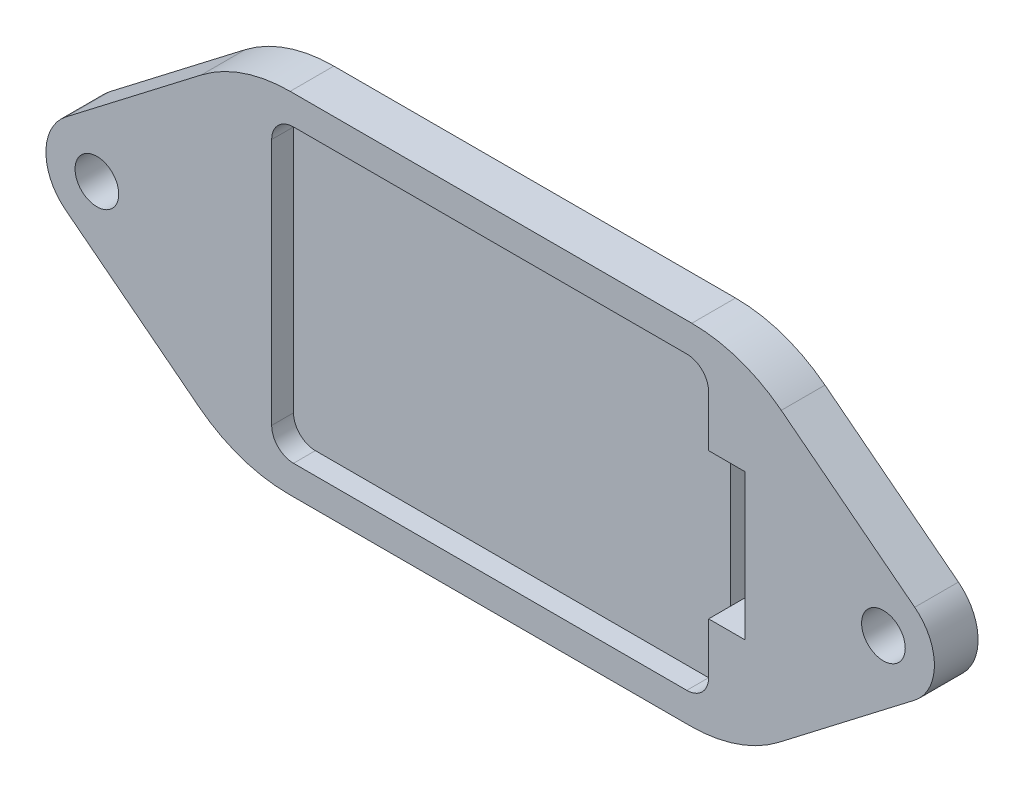
SolidWorks part; units mm, degrees
ref_plane "Front Plane" through (0, 0, 0) normal (0, 0, 1) x (1, 0, 0)
ref_plane "Top Plane" through (0, 0, 0) normal (0, 1, 0) x (1, 0, 0)
ref_plane "Right Plane" through (0, 0, 0) normal (1, 0, 0) x (0, 0, -1)
sketch "Sketch1" plane through (0, 0, 0) normal (0, 0, 1) x (1, 0, 0)
  line L0 (0, 20.0933) -> (0, -16.1178) construction
  line L1 (0, 0) -> (44.9398, 0) construction
  line L2 (-29.1329, 2.775) -> (-19.826, 9.9286)
  line L3 (-13.5, -10) -> (13.5, -10)
  line L4 (-15, -8.5) -> (-15, 8.5)
  line L5 (-13.5, 10) -> (13.5, 10)
  line L6 (15, -8.5) -> (15, 8.5)
  line L7 (-15, -10) -> (15, 10) construction
  line L8 (-15, 10) -> (15, -10) construction
  line L9 (-13.8471, -12) -> (13.7319, -12)
  line L11 (-13.7319, 12) -> (13.8471, 12)
  line L13 (-17.2799, -12) -> (17.2799, 12) construction
  line L14 (-17.131, 12) -> (17.131, -12) construction
  line L15 (-29.1496, -2.7621) -> (-19.9889, -9.8916)
  line L16 (19.826, -9.9286) -> (29.1329, -2.775)
  line L17 (19.9889, 9.8916) -> (29.1496, 2.7621)
  line L19 (17.5, -5) -> (15, -5)
  line L20 (17.5, -5) -> (17.5, 5)
  line L21 (17.5, 5) -> (15, 5)
  line L22 (15, -5) -> (15, 5)
  line L23 (17.5, -5) -> (15, 5) construction
  line L24 (17.5, 5) -> (15, -5) construction
  circle A0 centre (-27, 0) radius 1.5
  arc A1 (-29.1329, 2.775) -> (-29.1496, -2.7621) centre (-27, 0) ccw
  circle A2 centre (27, 0) radius 1.5
  arc A3 (29.1329, -2.775) -> (29.1496, 2.7621) centre (27, 0) ccw
  arc A4 (-13.8471, -12) -> (-19.9889, -9.8916) centre (-13.8471, -2) cw
  arc A5 (19.826, -9.9286) -> (13.7319, -12) centre (13.7319, -2) cw
  arc A6 (19.9889, 9.8916) -> (13.8471, 12) centre (13.8471, 2) ccw
  arc A7 (-13.7319, 12) -> (-19.826, 9.9286) centre (-13.7319, 2) ccw
  arc A8 (-13.5, -10) -> (-15, -8.5) centre (-13.5, -8.5) cw
  arc A9 (15, -8.5) -> (13.5, -10) centre (13.5, -8.5) cw
  arc A10 (15, 8.5) -> (13.5, 10) centre (13.5, 8.5) ccw
  arc A11 (-13.5, 10) -> (-15, 8.5) centre (-13.5, 8.5) ccw
  point P50 (16.25, 0)
  dimension "D1" = 3
  dimension "D2" = 7
  dimension "D4" = 10
  dimension "D8" = 1.5
  dimension "D3" = 27
  dimension "D5" = 20
  dimension "D6" = 2
  dimension "D7" = 30
  dimension "D9" = 10
  dimension "D10" = 2.5
extrude "Boss-Extrude1" add sketch "Sketch1" along normal blind 3 contours L11 A7 L2 A1 L15 A4 L9 A5 L16 A3 L17 A6 A11 L5 A10 L6 L21 L20 L19 A9 L3 A8 L4 A0 A2 region at (-24.08, 5.832, 0)
extrude "Boss-Extrude2" add sketch "Sketch1<3>" along normal blind 1.5 contours L5 A11 L4 A8 L3 A9 L6 A10 region at (0, 0, 0)
sketch "Sketch1<3>" plane through (0, 0, 0) normal (0, 0, 1) x (1, 0, 0) same geometry as "Sketch1"
